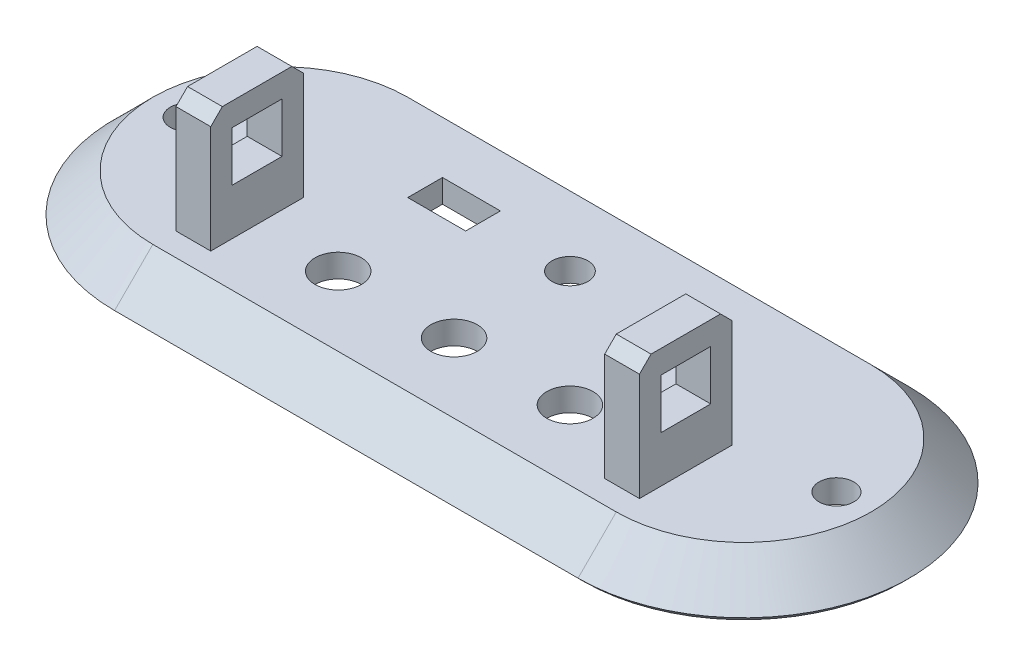
SolidWorks part; units mm, degrees
ref_plane "Plan de face" through (0, 0, 0) normal (0, 0, 1) x (1, 0, 0)
ref_plane "Plan de dessus" through (0, 0, 0) normal (0, 1, 0) x (1, 0, 0)
ref_plane "Plan de droite" through (0, 0, 0) normal (1, 0, 0) x (0, 0, -1)
sketch "Esquisse1" plane through (0, 0, 0) normal (0, 1, 0) x (1, 0, 0)
  line L0 (-20, 0) -> (20, 0) construction
  line L1 (-20, 14.8) -> (20, 14.8)
  line L2 (-20, -14.8) -> (20, -14.8)
  arc A0 (-20, 14.8) -> (-20, -14.8) centre (-20, 0) ccw
  arc A1 (20, -14.8) -> (20, 14.8) centre (20, 0) ccw
  point P3 (0, 0)
  dimension "D1" = 14.8
  dimension "D2" = 40
extrude "Boss.-Extru.1" add sketch "Esquisse1" along normal blind 3.8 draft 45
shell "Coque2" thickness 2 removed face at (0, 0, 0)
chamfer "Chanfrein1" distance 1 angle 45 4 edges at (-34.8, 0, 0) (0, 0, 14.8) (0, 0, -14.8) (34.8, 0, 0) first distance on face at (0, 0, 0)
sketch "Esquisse2" plane through (0, 3.8, 0) normal (0, 1, 0) x (1, 0, 0)
  line L0 (0, 11) -> (0, -11) construction
  line L1 (20, 11) -> (-20, 11) construction
  line L2 (-20, -11) -> (20, -11) construction
  circle A0 centre (-28, 0) radius 1.5
  circle A1 centre (28, 0) radius 1.5
  point P2 (0, 0)
  dimension "D1" = 3
  dimension "D2" = 8
extrude "Enlèv. mat.-Extru.1" cut sketch "Esquisse2" against normal up to next
sketch "Esquisse3" plane through (0, 1.8, 0) normal (0, -1, 0) x (1, 0, 0)
  line L0 (0, 0) -> (18.2371, 0) construction
  line L1 (-10, -6.5) -> (-10, -3.5) construction
  line L2 (-7.5, -3.5) -> (-12.5, -3.5)
  line L3 (-7.5, -3.5) -> (-7.5, -6.5)
  line L4 (-7.5, -6.5) -> (-12.5, -6.5)
  line L5 (-12.5, -3.5) -> (-12.5, -6.5)
  line L6 (-10, -5) -> (-7.5, -5) construction
  circle A0 centre (0, -5) radius 1.55
  circle A1 centre (10, 5) radius 2
  circle A2 centre (0, 5) radius 2
  circle A3 centre (-10, 5) radius 2
  dimension "D1" = 3.1
  dimension "D2" = 4
  dimension "D3" = 5
  dimension "D4" = 5
  dimension "D5" = 10
  dimension "D7" = 5
  dimension "D8" = 3
  dimension "D6" = 3
extrude "Enlèv. mat.-Extru.2" cut sketch "Esquisse3" against normal up to next
ref_plane "Plan1" through (20, 0, 0) normal (-1, 0, 0) x (0, 0, 1)
sketch "Esquisse4" plane through (20, 0, 0) normal (-1, 0, 0) x (0, 0, 1)
  line L0 (7, 3.8) -> (3, 3.8) construction
  line L1 (9, 3.8) -> (1, 3.8)
  line L2 (9, 3.8) -> (9, 14.1)
  line L3 (9, 14.1) -> (5, 14.1)
  line L4 (5, 3.8) -> (5, 7.8) construction
  line L5 (1, 3.8) -> (1, 14.1)
  line L6 (7.15, 7.8) -> (2.85, 7.8)
  line L7 (7.15, 7.8) -> (7.15, 12.1)
  line L8 (7.15, 12.1) -> (2.85, 12.1)
  line L9 (2.85, 7.8) -> (2.85, 12.1)
  line L11 (1, 14.1) -> (5, 14.1)
  point P15 (0, 0)
  dimension "D1" = 0
  dimension "D2" = 4
  dimension "D3" = 2
  dimension "D4" = 2.15
  dimension "D6" = 4.3
  dimension "D7" = 4
  dimension "D8" = 5
extrude "Boss.-Extru.2" add sketch "Esquisse4" along normal blind 3
chamfer "Chanfrein2" distance 1 angle 45 2 edges at (18.5, 14.1, 1) (18.5, 14.1, 9)
ref_plane "Plan2" through (-20, 0, 0) normal (1, 0, 0) x (0, 0, -1)
ref_plane "Plan3" through (0, 0, 0) normal (1, 0, 0) x (0, 0, -1)
mirror "Symétrie1" about plane through (0, 0, 0) normal (1, 0, 0) of "Chanfrein2", "Boss.-Extru.2"
